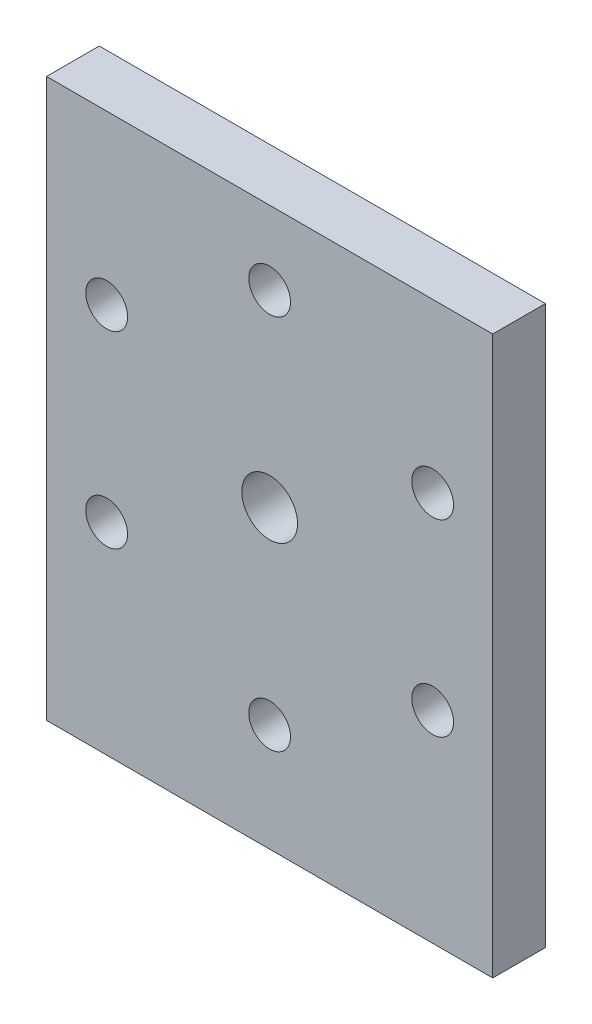
SolidWorks part; units mm, degrees
ref_plane "Front Plane" through (0, 0, 0) normal (0, 0, 1) x (1, 0, 0)
ref_plane "Top Plane" through (0, 0, 0) normal (0, 1, 0) x (1, 0, 0)
ref_plane "Right Plane" through (0, 0, 0) normal (1, 0, 0) x (0, 0, -1)
sketch "Sketch1" plane through (0, 0, 0) normal (0, 0, 1) x (1, 0, 0)
  line L1 (-50.8, 127) -> (50.8, 127)
  line L2 (-50.8, 127) -> (-50.8, 0)
  line L3 (-50.8, 0) -> (50.8, 0)
  line L4 (50.8, 127) -> (50.8, 0)
  circle A0 centre (0, 67.375) radius 6.35
  circle A1 centre (-37.12, 45.9437) radius 4.7625
  circle A2 centre (37.12, 45.9437) radius 4.7625
  circle A3 centre (0, 24.5125) radius 4.7625
  circle A4 centre (-37.12, 88.8062) radius 4.7625
  circle A5 centre (37.12, 88.8062) radius 4.7625
  circle A6 centre (0, 110.2375) radius 4.7625
  dimension "D1" = 127
  dimension "D3" = 12.7
  dimension "D4" = 42.8625
  dimension "D6" = 9.525
  dimension "D7" = 9.525
  dimension "D8" = 9.525
  dimension "D9" = 9.525
  dimension "D10" = 9.525
  dimension "D11" = 9.525
  dimension "D2" = 101.6
  dimension "D5" = 67.375
extrude "Boss-Extrude1" add sketch "Sketch1" along normal blind 12
